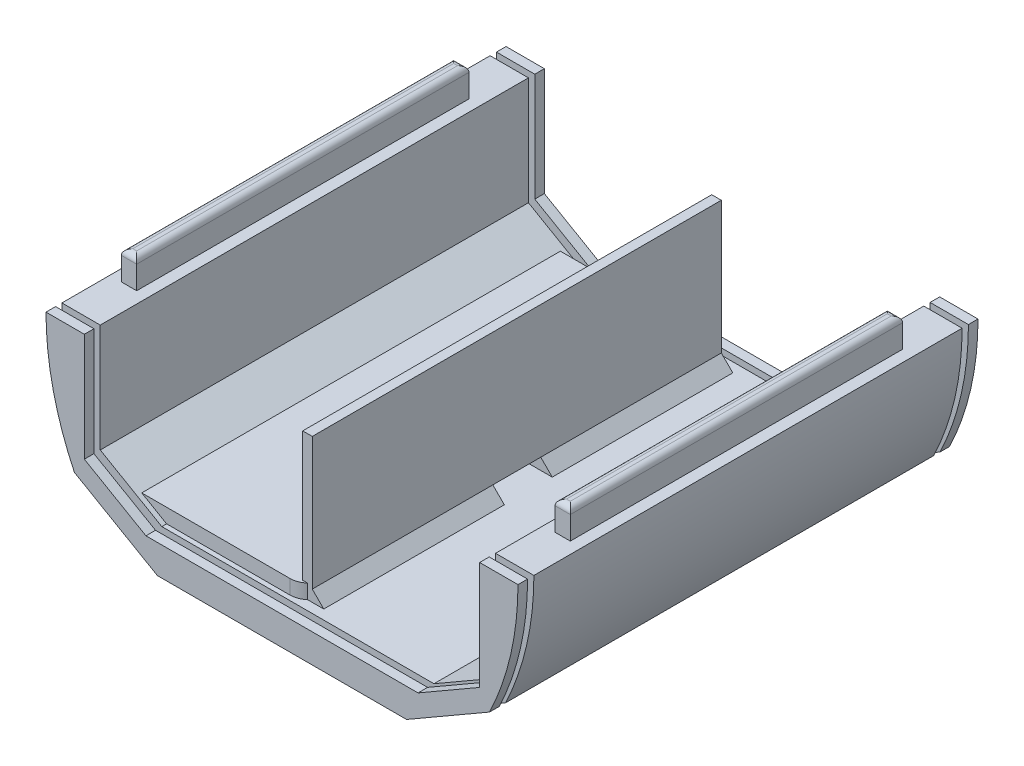
SolidWorks part; units mm, degrees
ref_plane "Front Plane" through (0, 0, 0) normal (0, 0, 1) x (1, 0, 0)
ref_plane "Top Plane" through (0, 0, 0) normal (0, 1, 0) x (1, 0, 0)
ref_plane "Right Plane" through (0, 0, 0) normal (1, 0, 0) x (0, 0, -1)
sketch "Sketch1" plane through (0, 0, 0) normal (0, 0, 1) x (1, 0, 0)
  line L0 (-65, 90) -> (-108.3013, 65)
  line L1 (-65, -90) -> (65, -90)
  line L3 (-65, 90) -> (65, 90)
  line L5 (-65, -90) -> (65, 90) construction
  line L6 (-65, 90) -> (65, -90) construction
  line L7 (-65, -90) -> (-108.3013, -65)
  line L8 (65, 90) -> (108.3013, 65)
  line L9 (65, -90) -> (108.3013, -65)
  arc A1 (-108.3013, 65) -> (-108.3013, -65) centre (26.8838, 0) ccw
  arc A4 (108.3013, 65) -> (108.3013, -65) centre (-26.8838, 0) cw
  point P0 (0, 0)
  point P7 (0, -90)
  dimension "D13" = 150
  dimension "D14" = 150
  dimension "D1" = 180
  dimension "D2" = 130
  dimension "D3" = 130
  dimension "D4" = 0
  dimension "D5" = 50
  dimension "D6" = 150
  dimension "D7" = 50
  dimension "D8" = 150
  dimension "D9" = 50
  dimension "D10" = 150
  dimension "D11" = 50
  dimension "D12" = 150
extrude "Boss-Extrude1" add sketch "Sketch1" along normal blind 240
sketch "Sketch2" plane through (0, 0, 240) normal (0, 0, 1) x (1, 0, 0)
  line L0 (-70.9808, 75) -> (70.9808, 75)
  line L1 (70.9808, 75) -> (103.1162, 56.4466)
  line L3 (65, 90) -> (-65, 90) construction
  line L4 (-70.9808, -75) -> (70.9808, -75)
  line L5 (70.9808, -75) -> (103.1162, -56.4466)
  line L6 (-65, -90) -> (65, -90) construction
  line L7 (108.3013, 65) -> (65, 90) construction
  line L8 (65, -90) -> (108.3013, -65) construction
  line L9 (-70.9808, 75) -> (-103.1162, 56.4466)
  line L10 (-70.9808, -75) -> (-103.1162, -56.4466)
  line L13 (-65, 90) -> (-108.3013, 65) construction
  line L15 (-108.3013, -65) -> (-65, -90) construction
  line L16 (-103.1162, 56.4466) -> (-103.1162, -56.4466)
  line L17 (103.1162, 56.4466) -> (103.1162, -56.4466)
  arc A0 (-108.3013, 65) -> (-108.3013, -65) centre (26.8838, 0) ccw construction
  arc A1 (108.3013, -65) -> (108.3013, 65) centre (-26.8838, 0) ccw construction
  point P24 (-123.1162, 0)
  point P28 (123.1162, 0)
  dimension "D1" = 15
  dimension "D2" = 10
  dimension "D3" = 20
  dimension "D4" = 15
  dimension "D5" = 20
  dimension "D7" = 10
  dimension "D8" = 10
  dimension "D10" = 10
sketch "Sketch3" plane through (0, 0, 0) normal (1, 0, 0) x (0, 0, -1)
  line L0 (-240, 90) -> (0, 90) construction
  line L1 (-235, 85) -> (-231.7, 85)
  line L2 (-235, 85) -> (-235, -85)
  line L3 (-235, -85) -> (-231.7, -85)
  line L4 (-231.7, 85) -> (-231.7, -85)
  line L5 (-240, -90) -> (0, -90) construction
  line L6 (-240, 65) -> (-240, -65) construction
  line L8 (-8.3, 85) -> (-5, 85)
  line L9 (-8.3, 85) -> (-8.3, -85)
  line L10 (-8.3, -85) -> (-5, -85)
  line L11 (-5, 85) -> (-5, -85)
  line L12 (0, -65) -> (0, 65) construction
  dimension "D1" = 5
  dimension "D2" = 5
  dimension "D3" = 5
  dimension "D4" = 3.3
  dimension "D5" = 5
  dimension "D6" = 5
  dimension "D7" = 5
  dimension "D8" = 3.3
extrude "Cut-Extrude4" cut sketch "Sketch2" against normal through all both and the other way through all
extrude "Cut-Extrude5" cut sketch "Sketch3" against normal through all both and the other way through all
sketch "Sketch7" plane through (0, 0, 0) normal (1, 0, 0) x (0, 0, -1)
  line L0 (-231.7, 65) -> (-231.7, -65) construction
  line L1 (-226.7, 45) -> (-13.3, 45)
  line L2 (-226.7, 45) -> (-226.7, 50)
  line L3 (-226.7, 50) -> (-13.3, 50)
  line L4 (-13.3, 45) -> (-13.3, 50)
  line L5 (-226.7, 45) -> (-13.3, 50) construction
  line L6 (-226.7, 50) -> (-13.3, 45) construction
  line L7 (-8.3, -65) -> (-8.3, 65) construction
  line L8 (-8.3, 75) -> (-231.7, 75) construction
  point P0 (-120, 47.5)
  dimension "D1" = 5
  dimension "D2" = 5
  dimension "D3" = 5
  dimension "D4" = 25
extrude "Boss-Extrude4" add sketch "Sketch7" along normal up to surface and the other way up to surface up to face at (103.1162, 0, 120) other way up to face at (-103.1162, 0, 120)
chamfer "Chamfer7" distance 6 angle 45 2 edges at (103.1162, 45, 120) (-103.1162, 45, 120)
sketch "Sketch8" plane through (0, -75, 0) normal (0, 1, 0) x (1, 0, 0)
  line L0 (-73.6603, -8.3) -> (-108.3013, -8.3) construction
  line L1 (-2.5, -226.7) -> (2.5, -226.7)
  line L2 (-2.5, -226.7) -> (-2.5, -13.3)
  line L3 (-2.5, -13.3) -> (2.5, -13.3)
  line L4 (2.5, -226.7) -> (2.5, -13.3)
  line L5 (-2.5, -226.7) -> (2.5, -13.3) construction
  line L6 (-2.5, -13.3) -> (2.5, -226.7) construction
  line L7 (-108.3013, -231.7) -> (-73.6603, -231.7) construction
  point P0 (0, -120)
  dimension "D1" = 5
  dimension "D2" = 5
  dimension "D3" = 5
extrude "Boss-Extrude5" add sketch "Sketch8" along normal up to surface (120 mm away) up to face at (0, 45, 120)
chamfer "Chamfer8" distance 6 angle 45 4 edges at (-2.5, 45, 120) (2.5, 45, 120) (2.5, -75, 120) (-2.5, -75, 120)
sketch "Sketch10" plane through (0, 0, 0) normal (1, 0, 0) x (0, 0, -1)
  line L0 (-240, -90) -> (0, -90) construction
  line L1 (-132.5, -75) -> (-107.5, -75)
  line L2 (-132.5, -75) -> (-132.5, -69)
  line L3 (-132.5, -69) -> (-107.5, -69)
  line L4 (-107.5, -75) -> (-107.5, -69)
  line L5 (-132.5, -75) -> (-107.5, -69) construction
  line L6 (-132.5, -69) -> (-107.5, -75) construction
  line L7 (-13.3, -75) -> (-226.7, -75) construction
  line L8 (-226.7, -69) -> (-13.3, -69) construction
  point P0 (-120, -72)
  point P7 (-120, -90)
  point P8 (-120, -75)
  dimension "D1" = 0
  dimension "D2" = 0
  dimension "D3" = 0
  dimension "D4" = 25
extrude "Cut-Extrude6" cut sketch "Sketch10" against normal blind 176 and the other way blind 23
sketch "Sketch12" plane through (0, 0, 0) normal (1, 0, 0) x (0, 0, -1)
  line L5 (-10.8, -67.5) -> (-229.2, -67.5)
  line L6 (-229.2, -67.5) -> (-229.2, -75)
  line L7 (-229.2, -75) -> (-132.5, -75)
  line L8 (-132.5, -75) -> (-132.5, -69)
  line L9 (-132.5, -69) -> (-107.5, -69)
  line L10 (-107.5, -69) -> (-107.5, -75)
  line L11 (-107.5, -75) -> (-10.8, -75)
  line L13 (-231.7, 56.4466) -> (-231.7, -56.4466) construction
  line L15 (-8.3, -75) -> (-107.5, -75) construction
  line L16 (-240, -90) -> (0, -90) construction
  line L17 (-10.8, -75) -> (-10.8, -67.5)
  line L18 (-8.3, -85) -> (-8.3, -65) construction
  point P16 (-120, -69)
  point P19 (-120, -90)
  dimension "D1" = 7.5
  dimension "D2" = 2.5
  dimension "D3" = 2.5
  dimension "D4" = 0
  dimension "D5" = 0
  dimension "D6" = 25
  dimension "D7" = 6
  dimension "D8" = 6
extrude "Boss-Extrude6" add sketch "Sketch12" against normal blind 90
fillet "Fillet1" radius 10 1 edges at (0, -71.25, 10.8)
fillet "Fillet2" radius 10 1 edges at (0, -71.25, 229.2)
sketch "Sketch13" plane through (0, 0, 0) normal (1, 0, 0) x (0, 0, -1)
  line L0 (-240, 90) -> (0, 90) construction
  line L1 (-8.3, 75) -> (-231.7, 75) construction
  circle A0 centre (-173.35, 62.5) radius 1.2
  circle A1 centre (-66.65, 62.5) radius 1.2
  point P6 (-120, 90)
  dimension "D1" = 53.35
  dimension "D5" = 2.4
  dimension "D6" = 2.4
  dimension "D2" = 53.35
  dimension "D3" = 12.5
  dimension "D4" = 12.5
extrude "Cut-Extrude7" cut sketch "Sketch13" against normal through all
sketch "Sketch14" plane through (0, 50, 0) normal (0, 1, 0) x (1, 0, 0)
  line L0 (103.1162, -226.7) -> (-103.1162, -226.7) construction
  line L1 (-2.5, -226.7) -> (-2.5, -13.3) construction
  circle A0 centre (-41.18, -120) radius 2
  dimension "D1" = 4
  dimension "D2" = 106.7
  dimension "D3" = 38.68
extrude "Cut-Extrude8" cut sketch "Sketch14" against normal blind 47
sketch "Sketch15" plane through (0, 0, 0) normal (0, 0, 1) x (1, 0, 0)
  line L1 (-134.8254, 99.1586) -> (137.6079, 99.1586)
  line L2 (-134.8254, 99.1586) -> (-134.8254, 0)
  line L3 (-134.8254, 0) -> (137.6079, 0)
  line L4 (137.6079, 99.1586) -> (137.6079, 0)
extrude "Cut-Extrude9" cut sketch "Sketch15" against normal through all both and the other way through all
sketch "Sketch16" plane through (0, 0, 0) normal (0, 1, 0) x (1, 0, 0)
  line L5 (-123.1162, -8.3) -> (-103.1162, -8.3) construction
  line L6 (-117.1162, -33.3) -> (-109.1162, -33.3)
  line L7 (-117.1162, -33.3) -> (-117.1162, -206.7)
  line L8 (-117.1162, -206.7) -> (-109.1162, -206.7)
  line L9 (-109.1162, -33.3) -> (-109.1162, -206.7)
  line L10 (-103.1162, -8.3) -> (-103.1162, -231.7) construction
  line L11 (-123.1162, -231.7) -> (-123.1162, -8.3) construction
  line L12 (123.1162, -231.7) -> (103.1162, -231.7) construction
  line L13 (109.1162, -206.7) -> (117.1162, -206.7)
  line L14 (109.1162, -206.7) -> (109.1162, -33.3)
  line L15 (109.1162, -33.3) -> (117.1162, -33.3)
  line L16 (117.1162, -206.7) -> (117.1162, -33.3)
  line L17 (103.1162, -8.3) -> (123.1162, -8.3) construction
  line L18 (103.1162, -231.7) -> (103.1162, -8.3) construction
  line L19 (123.1162, -8.3) -> (123.1162, -231.7) construction
  point P6 (-113.1162, -8.3)
  point P7 (-113.1162, -33.3)
  point P8 (-113.1162, -206.7)
  point P11 (-103.1162, -120)
  point P12 (-109.1162, -120)
  point P13 (-117.1162, -120)
  dimension "D1" = 6
  dimension "D2" = 25
  dimension "D3" = 25
  dimension "D4" = 25
  dimension "D5" = 6
  dimension "D6" = 6
extrude "Boss-Extrude7" add sketch "Sketch16" along normal blind 15
fillet "Fillet3" radius 3 8 edges at (113.1162, 15, 33.3) (113.1162, 15, 206.7) (117.1162, 15, 120) (109.1162, 15, 120) (-113.1162, 15, 33.3) (-113.1162, 15, 206.7) (-109.1162, 15, 120) (-117.1162, 15, 120)
